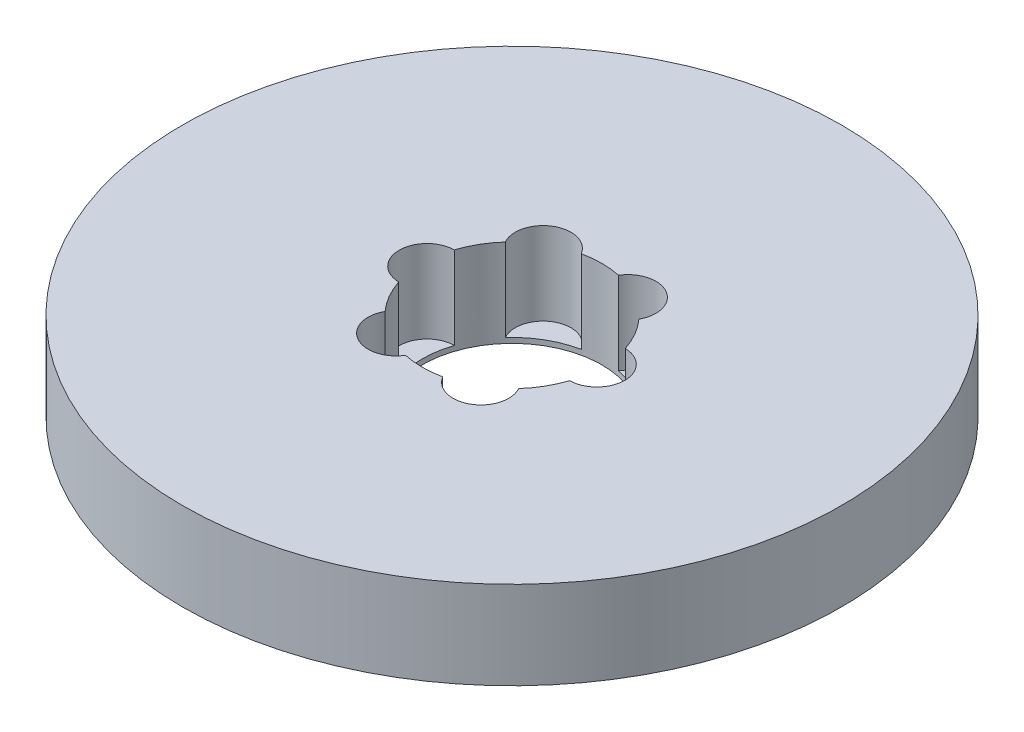
SolidWorks part; units mm, degrees
ref_plane "Front Plane" through (0, 0, 0) normal (0, 0, 1) x (1, 0, 0)
ref_plane "Top Plane" through (0, 0, 0) normal (0, 1, 0) x (1, 0, 0)
ref_plane "Right Plane" through (0, 0, 0) normal (1, 0, 0) x (0, 0, -1)
sketch "Sketch1" plane through (0, 0, 0) normal (0, 1, 0) x (1, 0, 0)
  circle A0 centre (0, 0) radius 82.5
  dimension "FLANGE_OD" = 165
extrude "Boss-Extrude1" add sketch "Sketch1" along normal blind 22
sketch "Sketch2" plane through (0, 0, 0) normal (0, 1, 0) x (1, 0, 0)
  circle A0 centre (0, 0) radius 22.5
  dimension "BORE_D" = 45
extrude "Cut-Extrude1" cut sketch "Sketch2" along normal through all
sketch "Sketch3" plane through (0, 22, 0) normal (0, 1, 0) x (1, 0, 0)
  circle A0 centre (0, 0) radius 21.2705 construction
  circle A1 centre (-21.2705, 0) radius 6.9636
  dimension "BOLT_D" = 13.9272
  dimension "BOLT_PCD" = 42.541
extrude "Cut-Extrude2" cut sketch "Sketch3" against normal blind 20.7123
pattern_circular "CirPattern1" count 6 over 360 about axis through (0, 0, 0) along (0, 1, 0) of "Cut-Extrude2"
